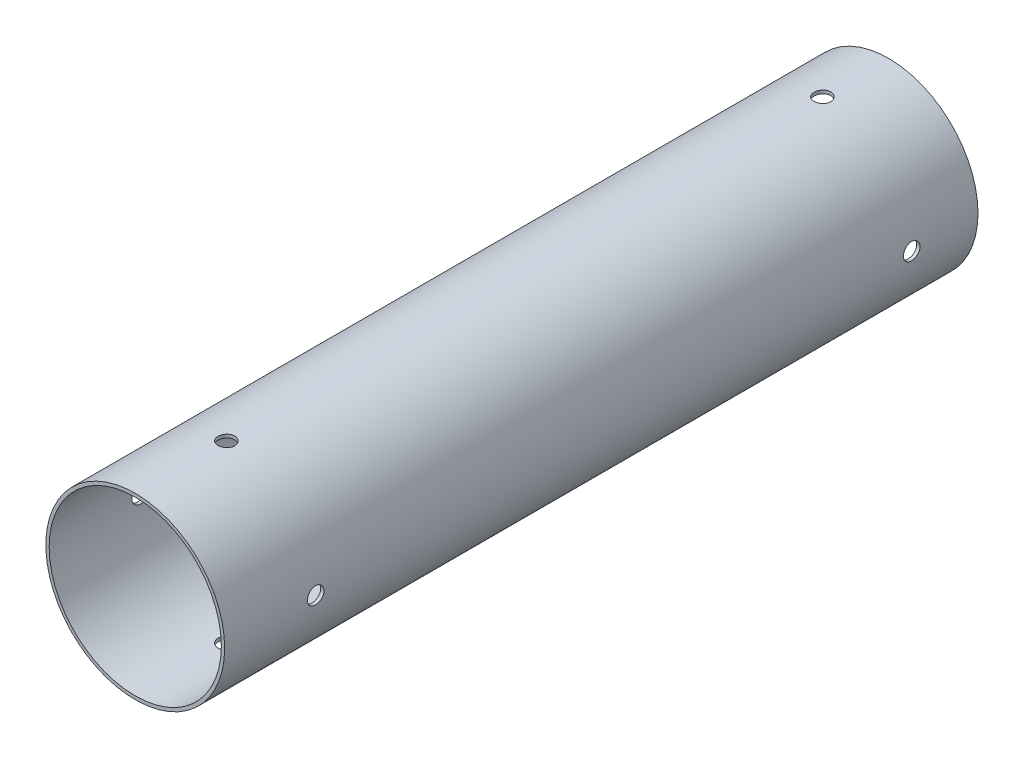
SolidWorks part; units mm, degrees
material "1060 Alloy"
ref_plane "Front Plane" through (0, 0, 0) normal (0, 0, 1) x (1, 0, 0)
ref_plane "Top Plane" through (0, 0, 0) normal (0, 1, 0) x (1, 0, 0)
ref_plane "Right Plane" through (0, 0, 0) normal (1, 0, 0) x (0, 0, -1)
sketch "Sketch1" plane through (0, 0, 0) normal (0, 0, 1) x (1, 0, 0)
  circle A0 centre (0, 0) radius 27
  circle A1 centre (0, 0) radius 26
  dimension "D1" = 54
  dimension "D2" = 52
extrude "Boss-Extrude1" add sketch "Sketch1" along normal blind 227.5
sketch "Sketch2" plane through (0, 0, 0) normal (0, 1, 0) x (1, 0, 0)
  line L0 (27, 0) -> (-27, 0) construction
  circle A0 centre (0, -20) radius 2.5
  dimension "D1" = 5
  dimension "D2" = 20
extrude "Cut-Extrude1" cut sketch "Sketch2" against normal up to next and the other way blind 1
sketch "Sketch3" plane through (0, 0, 0) normal (0, 1, 0) x (1, 0, 0)
  line L0 (0, -149.7653) -> (0, 20.6247) construction
pattern_linear "LPattern1" count 2 spacing 180 along (0, 0, 1) of "Cut-Extrude1"
pattern_circular "CirPattern2" count 4 over 360 about axis through (0, 0, 227.5) along (0, 0, -1) of "LPattern1"
